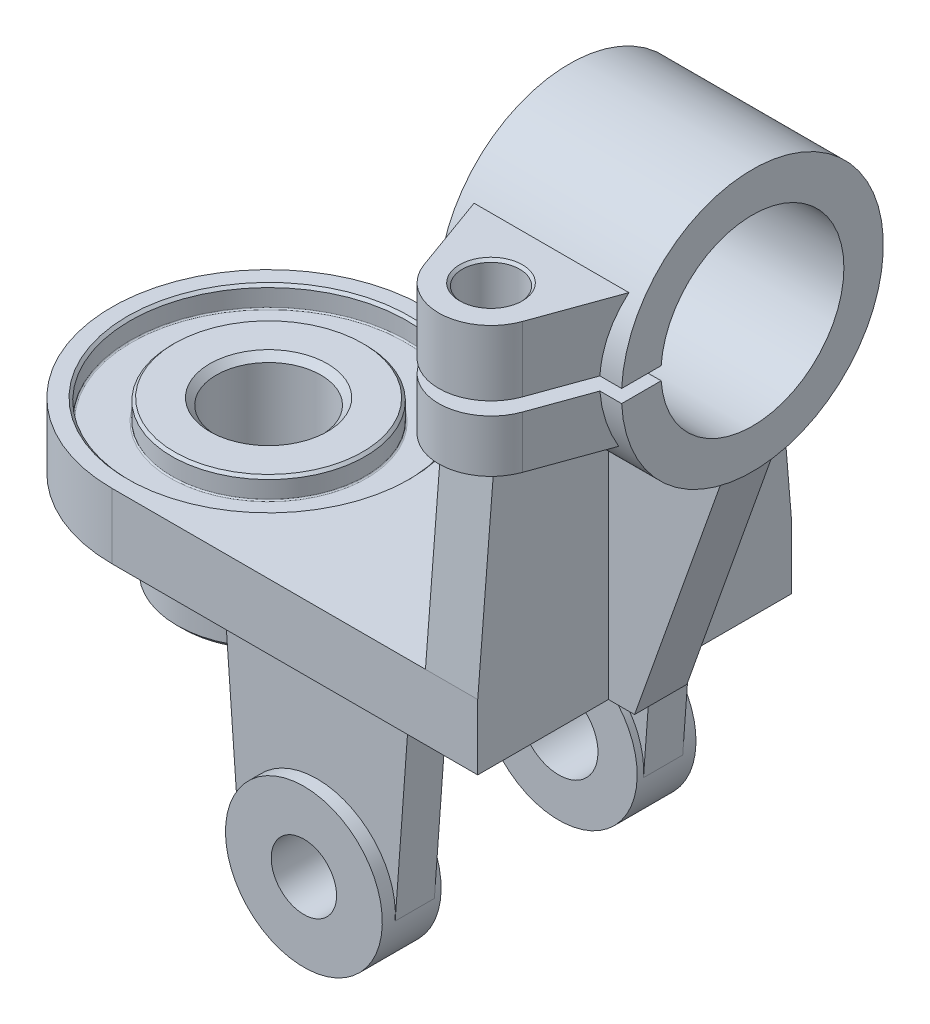
SolidWorks part; units mm, degrees
ref_plane "Спереди" through (0, 0, 0) normal (0, 0, 1) x (1, 0, 0)
ref_plane "Сверху" through (0, 0, 0) normal (0, 1, 0) x (1, 0, 0)
ref_plane "Справа" through (0, 0, 0) normal (1, 0, 0) x (0, 0, -1)
sketch "Эскиз1" plane through (0, 0, 0) normal (0, 0, 1) x (1, 0, 0)
  line L0 (0, 0) -> (0, -60) construction
  line L1 (-20, 0) -> (-37, 0)
  line L2 (-37, 0) -> (-37, -8)
  line L3 (-37, -8) -> (-53, -8)
  line L4 (-53, -8) -> (-53, 0)
  line L5 (-53, 0) -> (-60, 0)
  line L6 (-60, 0) -> (-60, -25)
  line L7 (-60, -25) -> (-35, -25)
  line L8 (-35, -25) -> (-35, -60)
  line L9 (-35, -60) -> (-20, -60)
  line L10 (-20, -60) -> (-20, 0)
  dimension "D1" = 20
  dimension "D2" = 37
  dimension "D3" = 53
  dimension "D4" = 8
  dimension "D5" = 60
  dimension "D6" = 25
  dimension "D7" = 60
  dimension "D8" = 35
revolve "Повернуть1" add sketch "Эскиз1" angle 360 about L0
chamfer "Фаска1" distance 2 angle 45 1 edges at (-35, -60, 0)
chamfer "Фаска2" distance 2.5 angle 45 1 edges at (-20, 0, 0)
chamfer "Фаска3" distance 1 angle 45 2 edges at (-53, 0, 0) (-37, 0, 0)
fillet "Скругление1" radius 0.5 2 edges at (-37, -8, 0) (-53, -8, 0)
sketch "Эскиз5" plane through (0, 0, 0) normal (0, 1, 0) x (1, 0, 0)
  line L0 (0, -60) -> (0, 60) construction
  line L1 (0, 60) -> (140, 60)
  line L2 (140, 60) -> (140, -60)
  line L3 (140, -60) -> (0, -60)
  circle A0 centre (0, 0) radius 60 construction
  arc A1 (0, -60) -> (0, 60) centre (0, 0) ccw
  point P10 (0, 0)
  dimension "D1" = 140
extrude "Бобышка-Вытянуть2" add sketch "Эскиз5" against normal blind 25
sketch "Эскиз6" plane through (0, 0, 0) normal (0, 1, 0) x (1, 0, 0)
  line L0 (140, 60) -> (140, -60)
  line L1 (140, -60) -> (120, -60)
  line L2 (140, -60) -> (0, -60) construction
  line L3 (120, -60) -> (120, 60)
  line L4 (0, 60) -> (140, 60) construction
  line L5 (120, 60) -> (140, 60)
  dimension "D1" = 20
extrude "Бобышка-Вытянуть3" add sketch "Эскиз6" along normal blind 118
sketch "Эскиз7" plane through (120, 0, 0) normal (-1, 0, 0) x (0, 0, 1)
  line L1 (-60, 118) -> (60, 118) construction
  line L2 (-60, 0) -> (-49.8275, 122.1496)
  line L3 (60, 0) -> (49.8275, 122.1496)
  line L4 (-60, 0) -> (-76.0972, 0)
  line L5 (-76.0972, 0) -> (-76.0972, 203.028)
  line L6 (-76.0972, 203.028) -> (78.2444, 203.028)
  line L7 (78.2444, 203.028) -> (78.2444, 0)
  line L8 (78.2444, 0) -> (60, 0)
  arc A1 (-49.8275, 122.1496) -> (49.8275, 122.1496) centre (0, 118) ccw
  dimension "D1" = 100
extrude "Вырез-Вытянуть1" cut sketch "Эскиз7" against normal blind 118
sketch "Эскиз9" plane through (120, 0, 0) normal (-1, 0, 0) x (0, 0, 1)
  line L0 (-50.1731, 118) -> (50, 118) construction
  circle A0 centre (-0.0865, 118) radius 50.0865
  circle A1 centre (-0.0865, 118) radius 35
  dimension "D1" = 70
extrude "Бобышка-Вытянуть5" add sketch "Эскиз9" along normal blind 5 and the other way blind 65 contours A0
sketch "Эскиз10" plane through (115, 0, 0) normal (-1, 0, 0) x (0, 0, 1)
  line L0 (50, 118) -> (-50.1731, 118) construction
  line L1 (34.8241, 120.5) -> (59.9135, 120.5)
  line L2 (34.8241, 115.5) -> (59.9135, 115.5)
  line L3 (59.9135, 120.5) -> (59.9135, 115.5)
  circle A0 centre (-0.0865, 118) radius 50.0865 construction
  arc A1 (-50.1731, 118) -> (50, 118) centre (-0.0865, 118) ccw construction
  arc A2 (34.8241, 120.5) -> (34.8241, 115.5) centre (-0.0865, 118) ccw
  dimension "D1" = 70
  dimension "D2" = 5
  dimension "D3" = 60
extrude "Вырез-Вытянуть4" cut sketch "Эскиз10" against normal blind 94 contours A2 L2 L3 L1
sketch "Эскиз11" plane through (115, 0, 0) normal (-1, 0, 0) x (0, 0, 1)
  line L6 (-0.0865, 82.3437) -> (-0.0865, 153.6563) construction
  line L7 (84.9135, 145.5) -> (84.9135, 95.5) construction
  line L8 (34.8241, 120.5) -> (84.9135, 120.5)
  line L9 (34.8241, 115.5) -> (84.9135, 115.5)
  line L10 (84.9135, 95.5) -> (26.723, 95.5)
  line L11 (84.9135, 145.5) -> (21.5641, 145.5)
  line L12 (84.9135, 145.5) -> (84.9135, 120.5)
  line L13 (84.9135, 115.5) -> (84.9135, 95.5)
  arc A3 (34.8241, 120.5) -> (34.8241, 115.5) centre (-0.0865, 118) ccw construction
  arc A4 (34.8241, 120.5) -> (21.5641, 145.5) centre (-0.0865, 118) ccw
  arc A5 (26.723, 95.5) -> (34.8241, 115.5) centre (-0.0865, 118) ccw
  point P12 (-0.0865, 118)
  dimension "D1" = 85
  dimension "D2" = 25
  dimension "D3" = 20
extrude "Бобышка-Вытянуть6" add sketch "Эскиз11" against normal blind 70 separate body
sketch "Эскиз12" plane through (0, 145.5, 0) normal (0, 1, 0) x (1, 0, 0)
  line L0 (115, -64.9135) -> (185, -64.9135) construction
  line L1 (115, -40.7306) -> (185, -40.7306) construction
  line L2 (115, -26.8884) -> (131.1895, -71.7081)
  line L3 (150, -64.9135) -> (150, -40.7306) construction
  line L4 (115, -21.5641) -> (115, -84.9135)
  line L5 (115, -84.9135) -> (185, -84.9135)
  line L6 (185, -84.9135) -> (185, -21.5641)
  line L7 (185, -21.5641) -> (115, -21.5641)
  line L8 (115, -21.5641) -> (115, -84.9135) construction
  line L9 (115, -84.9135) -> (185, -84.9135) construction
  line L10 (185, -84.9135) -> (185, -21.5641) construction
  line L11 (185, -21.5641) -> (115, -21.5641) construction
  line L12 (185, -26.8884) -> (168.8105, -71.7081)
  line L13 (150, -40.7306) -> (120, -40.7306) construction
  line L14 (113.0768, -21.5641) -> (115, -21.5641) construction
  line L15 (185, -21.5641) -> (186.9232, -21.5641) construction
  line L16 (115, -21.5641) -> (115, -26.8884)
  line L17 (185, -21.5641) -> (185, -26.8884)
  line L18 (115, -21.5641) -> (185, -21.5641)
  arc A0 (131.1895, -71.7081) -> (168.8105, -71.7081) centre (150, -64.9135) ccw
  dimension "D3" = 44.1829
  dimension "D2" = 20
  dimension "D4" = 30
  dimension "D1" = 0
extrude "Вырез-Вытянуть5" cut sketch "Эскиз12" against normal blind 70 flip side to cut
sketch "Эскиз13" plane through (0, 145.5, 0) normal (0, 1, 0) x (1, 0, 0)
  line L0 (115, -64.9135) -> (185, -64.9135) construction
  circle A0 centre (150, -64.9135) radius 11
  dimension "D1" = 22
extrude "Вырез-Вытянуть6" cut sketch "Эскиз13" against normal up to vertex (25 mm away) up to point (131.1895, 120.5, 71.7081)
sketch "Эскиз14" plane through (0, 95.5, 0) normal (0, -1, 0) x (1, 0, 0)
  circle A0 centre (150, 64.9135) radius 10
  dimension "D1" = 20
extrude "Вырез-Вытянуть7" cut sketch "Эскиз14" against normal up to vertex (20 mm away) up to point (131.1895, 115.5, 71.7081)
chamfer "Фаска4" distance 1 angle 45 1 edges at (150, 145.5, 75.9135)
combine bodies "Соединить2" operation type add bodies to combine 120 121 115
ref_plane "Плоскость1" through (73.5, 0, 0) normal (1, 0, 0) x (0, 0, -1)
sketch "Эскиз15" plane through (73.5, 0, 0) normal (1, 0, 0) x (0, 0, -1)
  line L0 (-60, -25) -> (60, -25) construction
  line L1 (-60, 0) -> (60, 0) construction
  line L2 (0, -25) -> (0, -92) construction
  line L3 (50.7, -92) -> (-50.7, -92) construction
  line L4 (60, -122) -> (37.5, -122)
  line L5 (-60, -92) -> (-37.5, -92)
  line L6 (-60, -92) -> (-60, -122)
  line L7 (-60, -122) -> (-37.5, -122)
  line L8 (-37.5, -92) -> (-37.5, -122)
  line L9 (37.5, -92) -> (37.5, -122)
  line L10 (60, -92) -> (37.5, -92)
  line L11 (60, -92) -> (60, -122)
  point P14 (0, -92)
  dimension "D1" = 92
  dimension "D2" = 75
  dimension "D3" = 120
  dimension "D4" = 30
revolve "Повернуть2" add sketch "Эскиз15" angle 360 about L3
sketch "Эскиз16" plane through (0, 0, 60) normal (0, 0, 1) x (1, 0, 0)
  line L0 (140, 0) -> (120, 0) construction
  line L1 (120, 0) -> (0, 0) construction
  line L2 (0, 0) -> (0, -25) construction
  line L3 (0, -25) -> (140, -25) construction
  line L4 (140, -25) -> (140, 0) construction
  line L5 (140, 0) -> (120, 0) construction
  line L6 (120, 0) -> (0, 0) construction
  line L7 (0, 0) -> (0, -25) construction
  line L8 (0, -25) -> (140, -25) construction
  line L9 (140, -25) -> (140, 0) construction
  line L11 (30.2863, -25) -> (131.814, -25)
  line L12 (30.2863, -25) -> (30.2863, -113.1765)
  line L13 (30.2863, -113.1765) -> (131.814, -113.1765)
  line L14 (131.814, -25) -> (131.814, -113.1765)
  circle A0 centre (73.5, -92) radius 30 construction
  circle A1 centre (73.5, -92) radius 30 construction
extrude "Бобышка-Вытянуть7" add sketch "Эскиз16" against normal blind 20 separate body
extrude "Вырез-Вытянуть8" cut sketch "Эскиз16<3>" against normal blind 5
sketch "Эскиз16<3>" plane through (0, 0, 60) normal (0, 0, 1) x (1, 0, 0) same geometry as "Эскиз16"
sketch "Эскиз17" plane through (0, 0, 55) normal (0, 0, 1) x (1, 0, 0)
  line L0 (140, 0) -> (120, 0) construction
  line L1 (120, 0) -> (0, 0) construction
  line L2 (0, 0) -> (0, -25) construction
  line L3 (0, -25) -> (140, -25) construction
  line L4 (140, -25) -> (140, 0) construction
  line L5 (140, 0) -> (120, 0)
  line L6 (120, 0) -> (0, 0)
  line L7 (0, 0) -> (0, -25)
  line L8 (0, -25) -> (140, -25)
  line L9 (140, -25) -> (140, 0)
  line L10 (73.5, -92) -> (73.5, -25) construction
  line L11 (73.5, -50) -> (73.5, 50) construction
  line L12 (38.5, -25) -> (43.5805, -94.1967)
  line L13 (108.5, -25) -> (103.4195, -94.1967)
  line L14 (38.5, -25) -> (108.5, -25)
  circle A0 centre (73.5, -92) radius 30 construction
  arc A1 (103.4195, -94.1967) -> (43.5805, -94.1967) centre (73.5, -92) ccw
  dimension "D1" = 35
extrude "Вырез-Вытянуть9" cut sketch "Эскиз17" against normal blind 31 flip side to cut contours A1 L10 L14 L12 | L10 A1 L13 L8 region at (91.5138, -47.2893, 55) region at (55.4862, -47.2893, 55)
mirror "Зеркальное отражение1" about plane through (0, 0, 0) normal (0, 0, 1) of bodies 127
combine bodies "Соединить3" operation type add bodies to combine 122 127 123 124 128
sketch "Эскиз18" plane through (0, 0, 60) normal (0, 0, 1) x (1, 0, 0)
  circle A0 centre (73.5, -92) radius 12.5
  circle A1 centre (73.5, -92) radius 30
  circle A2 centre (73.5, -92) radius 30 construction
  dimension "D2" = 25
  dimension "D1" = 0
extrude "Вырез-Вытянуть10" cut sketch "Эскиз18" against normal blind 31
sketch "Эскиз19" plane through (0, 0, -60) normal (0, 0, -1) x (-1, 0, 0)
  circle A0 centre (-73.5, -92) radius 15
  circle A1 centre (-73.5, -92) radius 30
  circle A2 centre (-73.5, -92) radius 30 construction
  dimension "D2" = 30
  dimension "D1" = 0
extrude "Вырез-Вытянуть11" cut sketch "Эскиз19" against normal blind 31
sketch "Эскиз20" plane through (0, 0, 0) normal (0, 0, 1) x (1, 0, 0)
  line L0 (185, 67.9135) -> (140, 67.9135) construction
  line L1 (140, 67.9135) -> (140, -25)
  line L2 (140, -25) -> (150, -25)
  line L3 (150, -25) -> (183, 67.9135)
  line L5 (140, 67.9135) -> (140, 73.4644)
  line L9 (183, 67.9135) -> (185, 73.5446)
  line L10 (185, 67.9135) -> (185, 168.0865) construction
  line L13 (185, 73.5446) -> (140, 73.4644)
  dimension "D1" = 10
  dimension "D2" = 2
extrude "Бобышка-Вытянуть10" add sketch "Эскиз20" along normal blind 10 and the other way blind 10 separate body
combine bodies "Соединить4" bodies to combine 132 131
